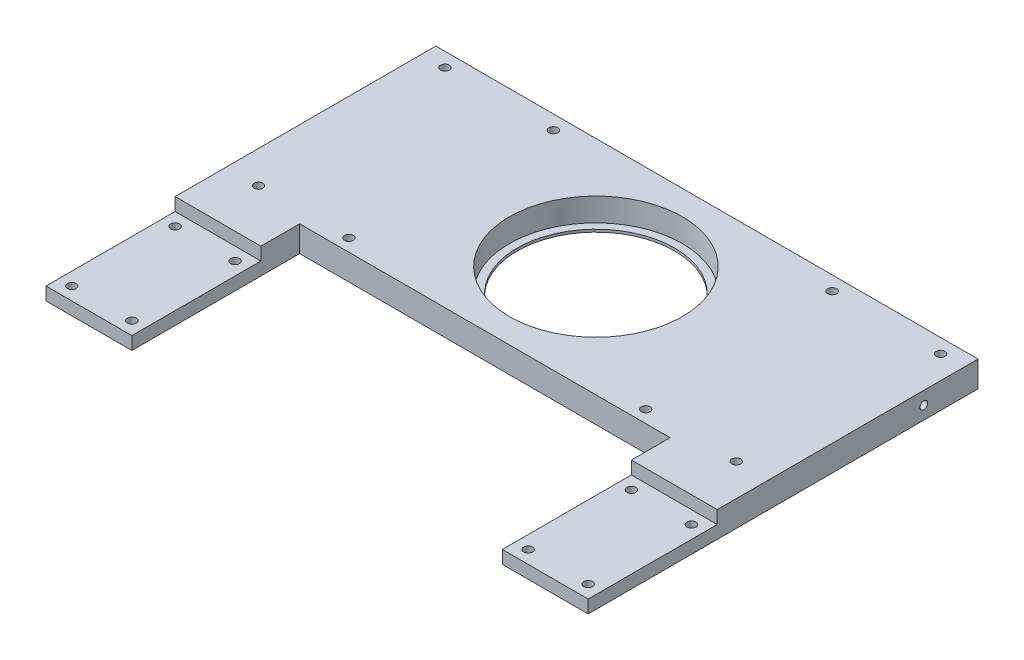
SolidWorks part; units mm, degrees
ref_plane "Ebene vorne" through (0, 0, 0) normal (0, 0, 1) x (1, 0, 0)
ref_plane "Ebene oben" through (0, 0, 0) normal (0, 1, 0) x (1, 0, 0)
ref_plane "Ebene rechts" through (0, 0, 0) normal (1, 0, 0) x (0, 0, -1)
sketch "Skizze1" plane through (0, 0, 0) normal (0, 1, 0) x (1, 0, 0)
  line L1 (-105, -200) -> (105, -200)
  line L2 (-105, -200) -> (-105, 200)
  line L3 (-105, 200) -> (105, 200)
  line L4 (105, -200) -> (105, 200)
  line L5 (-105, -200) -> (105, 200) construction
  line L6 (-105, 200) -> (105, -200) construction
  point P0 (0, 0)
  dimension "D1" = 210
  dimension "D2" = 400
extrude "Aufsatz-Linear austragen1" add sketch "Skizze1" along normal blind 10
ref_plane "Ebene1" through (0, -92.6125, 77.7111) normal (0, -0.766, 0.6428) x (1, 0, 0)
sketch "Skizze2" plane through (0, -92.6125, 77.7111) normal (0, -0.766, 0.6428) x (1, 0, 0)
  line L1 (-105, 159.6368) -> (105, 159.6368) construction
  circle A0 centre (0, 139.6368) radius 5
  dimension "D1" = 10
  dimension "D2" = 20
extrude "Schnitt-Linear austragen1" [suppressed] cut sketch "Skizze2" against normal blind 30 and the other way blind 10
sketch "Skizze3" [suppressed] plane through (0, -67.9923, 57.0523) normal (0, -0.766, 0.6428) x (1, 0, 0)
  circle A0 centre (0, 101.3345) radius 5
  dimension "D1" = 10
extrude "Aufsatz-Linear austragen2" [suppressed] add sketch "Skizze3" along normal blind 0.1
sketch "Skizze4" plane through (0, -92.6125, 77.7111) normal (0, -0.766, 0.6428) x (1, 0, 0)
  line L0 (0, 159.6368) -> (0, 159.9002) construction
  line L1 (-105, 159.6368) -> (105, 159.6368) construction
  line L2 (-25, 159.6368) -> (-25, 194.6368)
  line L3 (-25, 194.6368) -> (25, 194.6368)
  line L4 (-25, 159.6368) -> (25, 159.6368)
  line L5 (25, 159.6368) -> (25, 194.6368)
  point P10 (0, 194.6368)
  dimension "D1" = 50
  dimension "D2" = 35
extrude "Aufsatz-Linear austragen3" [suppressed] add sketch "Skizze4" against normal blind 10 separate body
sketch "Skizze5" plane through (0, 10, 0) normal (0, 1, 0) x (1, 0, 0)
  line L0 (0, 0) -> (0, -200) construction
  line L1 (-105, -200) -> (105, -200) construction
  line L2 (105, -200) -> (18, -200)
  line L3 (-18, -200) -> (-105, -46)
  line L4 (-105, 200) -> (-105, -200) construction
  line L5 (-105, -46) -> (-105, -200)
  line L6 (-105, -200) -> (-18, -200)
  line L7 (105, -46) -> (105, -200)
  line L8 (18, -200) -> (105, -46)
  line L9 (-105, 200) -> (-105, 105)
  line L10 (-105, 105) -> (105, 105)
  line L11 (105, -200) -> (105, 200) construction
  line L12 (105, 105) -> (105, 200)
  line L13 (105, 200) -> (-105, 200)
  line L14 (71.7468, -46) -> (-71.7468, -46)
  line L15 (-71.7468, -46) -> (-2.8247, -168)
  line L16 (71.7468, -46) -> (2.8247, -168)
  line L17 (-2.8247, -168) -> (2.8247, -168)
  line L18 (2.8247, -168) -> (0, -173) construction
  line L19 (-2.8247, -168) -> (0, -173) construction
  point P27 (0, -46)
  dimension "D1" = 36
  dimension "D2" = 154
  dimension "D3" = 95
  dimension "D4" = 32
  dimension "D5" = 27
extrude "Schnitt-Linear austragen2" cut sketch "Skizze5" against normal blind 10
sketch "Skizze6" plane through (0, 10, 0) normal (0, 1, 0) x (1, 0, 0)
  line L0 (0, -200) -> (0, -168) construction
  line L1 (-18, -200) -> (18, -200) construction
  line L2 (-2.8247, -168) -> (2.8247, -168) construction
  line L3 (0, -186.59) -> (-21.075, -186.59) construction
  circle A0 centre (-11, -195) radius 1.7
  circle A1 centre (-11, -178.18) radius 1.7
  circle A2 centre (11, -195) radius 1.7
  circle A3 centre (11, -178.18) radius 1.7
  dimension "D1" = 3.4
  dimension "D2" = 11
  dimension "D3" = 5
  dimension "D4" = 13.41
extrude "Schnitt-Linear austragen3" cut sketch "Skizze6" against normal through all
sketch "Skizze7" plane through (0, 0, 0) normal (0, -1, 0) x (1, 0, 0)
  line L0 (-11, 195) -> (-11, 200) construction
  line L1 (-18, 200) -> (18, 200) construction
  line L2 (-11, 195) -> (-5.1092, 195) construction
  line L3 (-11, 198.4064) -> (-8.05, 196.7032)
  line L4 (-8.05, 196.7032) -> (-8.05, 193.2968)
  line L5 (-11, 191.5936) -> (-8.05, 193.2968)
  line L6 (-11, 191.5936) -> (-13.95, 193.2968)
  line L7 (-13.95, 196.7032) -> (-13.95, 193.2968)
  line L8 (-11, 198.4064) -> (-13.95, 196.7032)
  line L9 (0, 200) -> (0, 121.6034) construction
  line L10 (11, 195) -> (11, 178.18) construction
  line L11 (11, 186.59) -> (0, 186.59) construction
  line L12 (11, 198.4064) -> (8.05, 196.7032)
  line L13 (11, 191.5936) -> (8.05, 193.2968)
  line L14 (8.05, 196.7032) -> (8.05, 193.2968)
  line L15 (11, 191.5936) -> (13.95, 193.2968)
  line L16 (13.95, 196.7032) -> (13.95, 193.2968)
  line L17 (11, 198.4064) -> (13.95, 196.7032)
  line L18 (-8.05, 176.4768) -> (-8.05, 179.8832)
  line L19 (-11, 181.5864) -> (-13.95, 179.8832)
  line L20 (-11, 181.5864) -> (-8.05, 179.8832)
  line L21 (-13.95, 176.4768) -> (-13.95, 179.8832)
  line L22 (-11, 174.7736) -> (-13.95, 176.4768)
  line L23 (-11, 174.7736) -> (-8.05, 176.4768)
  line L24 (8.05, 176.4768) -> (8.05, 179.8832)
  line L25 (11, 181.5864) -> (8.05, 179.8832)
  line L26 (11, 181.5864) -> (13.95, 179.8832)
  line L27 (13.95, 176.4768) -> (13.95, 179.8832)
  line L28 (11, 174.7736) -> (13.95, 176.4768)
  line L29 (11, 174.7736) -> (8.05, 176.4768)
  point P10 (-8.05, 195)
  dimension "D1" = 120
  dimension "D2" = 5.9
extrude "Schnitt-Linear austragen4" cut sketch "Skizze7" against normal blind 4
sketch "Skizze8" plane through (0, 10, 0) normal (0, 1, 0) x (1, 0, 0)
  line L0 (105, 95.41) -> (78.872, 95.41) construction
  line L1 (105, -46) -> (105, 105) construction
  line L2 (-105, 105) -> (105, 105) construction
  dimension "D1" = 9.59
ref_plane "Ebene2" through (0, 52.8485, -44.3452) normal (0, 0.766, -0.6428) x (-1, 0, 0)
sketch "Skizze9" plane through (0, 52.8485, -44.3452) normal (0, 0.766, -0.6428) x (-1, 0, 0)
  line L0 (-105, -66.6604) -> (-78.872, -66.6604) construction
  line L1 (-105, 41.6659) -> (-105, -74.0068) construction
  line L2 (0, -45.2589) -> (0, -16.2619) construction
  circle A0 centre (-100, -66.6604) radius 1.7
  circle A1 centre (100, -66.6604) radius 1.7
  circle A2 centre (-30, -66.6604) radius 1.7
  circle A3 centre (30, -66.6604) radius 1.7
  dimension "D1" = 3.4
  dimension "D2" = 5
  dimension "D3" = 30
extrude "Schnitt-Linear austragen5" [suppressed] cut sketch "Skizze9" against normal through all and the other way through all
ref_plane "Ebene3" through (0, 45.1881, -37.9173) normal (0, 0.766, -0.6428) x (-1, 0, 0)
sketch "Skizze10" [suppressed] plane through (0, 55.0361, -46.1808) normal (0, 0.766, -0.6428) x (-1, 0, 0)
  line L0 (-95, -81.9813) -> (-100, -81.9813) construction
  line L1 (-95, -81.9813) -> (-95, -30.0694) construction
  line L2 (-95, -78.7482) -> (-97.8, -80.3647)
  line L3 (-97.8, -80.3647) -> (-97.8, -83.5979)
  line L4 (-95, -85.2145) -> (-97.8, -83.5979)
  line L5 (-95, -85.2145) -> (-92.2, -83.5979)
  line L6 (-92.2, -80.3647) -> (-92.2, -83.5979)
  line L7 (-95, -78.7482) -> (-92.2, -80.3647)
  line L8 (0, 0) -> (0, -45.6283) construction
  line L9 (-30, -81.9813) -> (-95, -81.9813) construction
  line L10 (-62.5, -81.9813) -> (-62.5, -23.1343) construction
  line L11 (-32.8, -80.3647) -> (-32.8, -83.5979)
  line L12 (-30, -85.2145) -> (-32.8, -83.5979)
  line L13 (-30, -85.2145) -> (-27.2, -83.5979)
  line L14 (-27.2, -80.3647) -> (-27.2, -83.5979)
  line L15 (-30, -78.7482) -> (-27.2, -80.3647)
  line L16 (-30, -78.7482) -> (-32.8, -80.3647)
  line L17 (95, -78.7482) -> (92.2, -80.3647)
  line L18 (92.2, -80.3647) -> (92.2, -83.5979)
  line L19 (95, -85.2145) -> (92.2, -83.5979)
  line L20 (95, -85.2145) -> (97.8, -83.5979)
  line L21 (97.8, -80.3647) -> (97.8, -83.5979)
  line L22 (95, -78.7482) -> (97.8, -80.3647)
  line L23 (30, -78.7482) -> (32.8, -80.3647)
  line L24 (30, -78.7482) -> (27.2, -80.3647)
  line L25 (27.2, -80.3647) -> (27.2, -83.5979)
  line L26 (30, -85.2145) -> (27.2, -83.5979)
  line L27 (30, -85.2145) -> (32.8, -83.5979)
  line L28 (32.8, -80.3647) -> (32.8, -83.5979)
  point P9 (-97.8, -81.9813)
  point P31 (97.8, -81.9813)
  dimension "D1" = 120
  dimension "D2" = 5.6
extrude "Schnitt-Linear austragen6" [suppressed] cut sketch "Skizze10" against normal blind 10 and the other way blind 5
sketch "Skizze13" plane through (0, 10, 0) normal (0, 1, 0) x (1, 0, 0)
  line L0 (71.7468, -46) -> (105, -46) construction
  line L1 (71.7468, -46) -> (96.9548, -60.2409) construction
  line L2 (105, -46) -> (18, -200) construction
  line L3 (0, 0) -> (0, -38.1435) construction
  line L4 (2.8247, -168) -> (71.7468, -46) construction
  line L5 (84.3508, -53.1205) -> (104.4794, -17.4905) construction
  line L6 (105, -46) -> (105, 105) construction
  line L7 (88.3734, -46) -> (88.3734, -1) construction
  line L8 (99, -48.9512) -> (101.4769, -44.5668) construction
  line L9 (87.7845, -76.4734) -> (62.5765, -62.2325) construction
  line L10 (77.1638, -70.4734) -> (91.1741, -70.4734) construction
  circle A0 centre (99, -48.9512) radius 1.7
  circle A1 centre (76.9708, -48.9512) radius 1.7
  circle A2 centre (86.8414, -70.4734) radius 1.7
  circle A3 centre (-86.8414, -70.4734) radius 1.7
  circle A4 centre (-99, -48.9512) radius 1.7
  circle A5 centre (-76.9708, -48.9512) radius 1.7
  dimension "D1" = 6
  dimension "D5" = 35
  dimension "D3" = 3.4
  dimension "D6" = 3.4
  dimension "D2" = 6
  dimension "D4" = 6
extrude "Schnitt-Linear austragen7" [suppressed] cut sketch "Skizze13" against normal through all
sketch "Skizze14" plane through (99.2964, 0, 56.096) normal (0.8707, 0, 0.4919) x (0.4919, 0, -0.8707)
  line L0 (-23.4043, 5) -> (-23.4043, 10)
  line L5 (11.5957, 0) -> (11.5957, 10) construction
  line L6 (-23.4043, 5) -> (11.5957, 5)
  line L7 (11.5957, 10) -> (-165.2799, 10) construction
  line L8 (-23.4043, 10) -> (11.5957, 10)
  line L9 (11.5957, 10) -> (11.5957, 5)
  dimension "D1" = 35
extrude "Schnitt-Linear austragen8" [suppressed] cut sketch "Skizze14" against normal up to surface (28.9525 mm away)
mirror "Spiegeln1" [suppressed] about plane through (0, 0, 0) normal (1, 0, 0)
sketch "Skizze15" [suppressed] plane through (95, 0, 0) normal (1, 0, 0) x (0, 0, -1)
  line L0 (4, 10) -> (4, 0)
  line L1 (4, 0) -> (65, 0)
  line L2 (65, 0) -> (65, 10)
  line L3 (65, 10) -> (4, 10)
extrude "Schnitt-Linear austragen9" [suppressed] cut sketch "Skizze15" against normal through all
sketch "Skizze16" plane through (0, 0, 0) normal (0, -1, 0) x (1, 0, 0)
  line L0 (0, 200) -> (0, 168) construction
  line L1 (-18, 200) -> (18, 200) construction
  line L2 (-2.8247, 168) -> (2.8247, 168) construction
  line L3 (11, 186.59) -> (0, 186.59) construction
  line L4 (11, 195) -> (11, 178.18) construction
  line L6 (-17.5, 183.09) -> (17.5, 183.09)
  line L7 (-17.5, 183.09) -> (-17.5, 190.09)
  line L8 (-17.5, 190.09) -> (17.5, 190.09)
  line L9 (17.5, 183.09) -> (17.5, 190.09)
  line L10 (-17.5, 183.09) -> (17.5, 190.09) construction
  line L11 (-17.5, 190.09) -> (17.5, 183.09) construction
  dimension "D1" = 7
  dimension "D2" = 35
extrude "Schnitt-Linear austragen10" cut sketch "Skizze16" against normal blind 5
sketch "Skizze17" plane through (17.5, 0, 0) normal (-1, 0, 0) x (0, 0, 1)
  line L0 (186.59, 0) -> (186.59, 11.1261) construction
  line L1 (183.09, 0) -> (190.09, 0) construction
  line L2 (183.09, 5) -> (186.59, 8.5)
  line L3 (186.59, 8.5) -> (190.09, 5)
  line L4 (190.09, 5) -> (183.09, 5)
  dimension "D1" = 90
extrude "Schnitt-Linear austragen11" cut sketch "Skizze17" along normal up to surface (35 mm away) up to face at (-17.5, 2.5, 186.59)
sketch "Skizze18" [suppressed] plane through (0, 10, 0) normal (0, 1, 0) x (1, 0, 0)
  line L0 (0, -210) -> (0, 0) construction
  line L1 (-18, -210) -> (18, -210) construction
  line L2 (62.5765, -72.2325) -> (35.4483, -67.5372)
  line L3 (15.3378, -155.8503) -> (-22.1774, -134.6566)
  line L4 (2.8247, -178) -> (62.5765, -72.2325) construction
  line L5 (-15.3378, -155.8503) -> (22.1774, -134.6566)
  line L6 (58.6594, -79.166) -> (40.7308, -76.063)
  line L7 (0, -147.1854) -> (19.5429, -147.1854) construction
  line L8 (0, -95.4) -> (31.4297, -95.4) construction
  line L9 (11.6488, -162.3803) -> (0, -155.7995)
  line L10 (-71.7468, -56) -> (-2.8247, -178) construction
  line L11 (0, -95.4) -> (-37.5153, -116.5937) construction
  line L12 (-37.5153, -116.5937) -> (-39.2566, -117.5774) construction
  line L13 (-11.6488, -162.3803) -> (0, -155.7995)
  line L14 (-58.6594, -79.166) -> (-40.7308, -76.063)
  line L15 (-62.5765, -72.2325) -> (-35.4483, -67.5372)
  circle A0 centre (0, -95.4) radius 33.5
  arc A1 (7.4594, -151.3994) -> (7.4594, -142.9713) centre (9.84, -147.1854) cw
  arc A2 (-7.4594, -151.3994) -> (-7.4594, -142.9713) centre (-9.84, -147.1854) ccw
  circle A3 centre (0, -95.4) radius 45.0879
  point P17 (0, -147.1854)
  point P36 (5, -147.1854)
  point P40 (-5, -147.1854)
  line M16 (62.5765, -72.2325) -> (2.8247, -178)
  line M18 (-2.8247, -178) -> (-71.7468, -56)
  dimension "D2" = 67
  dimension "D5" = 2
  dimension "D4" = 10
  dimension "D1" = 114.6
  dimension "D3" = 7.5
  dimension "D6" = 7.5
extrude "Aufsatz-Linear austragen4" [suppressed] add sketch "Skizze18" against normal blind 10 contours A3 L15 L14 M18 | A3 A0 M16 M18 | A3 L6 L2 M16 | A2 L5 L3 | A3 L3 L5 | L3 A1 L5 | L13 L9 L3 L5 M18 M16
sketch "Skizze19" [suppressed] plane through (0, 0, 0) normal (0, -1, 0) x (1, 0, 0)
  circle A0 centre (0, 35.4) radius 31.5
  circle A1 centre (0, 35.4) radius 33.5
  circle A2 centre (0, 35.4) radius 33.5 construction
  dimension "D1" = 63
extrude "Aufsatz-Linear austragen5" [suppressed] add sketch "Skizze19" against normal blind 1
sketch "Skizze20" plane through (0, 10, 0) normal (0, 1, 0) x (1, 0, 0)
  line L0 (105, 99.52) -> (55.4083, 99.52) construction
  line L1 (105, -46) -> (105, 105) construction
  line L2 (-105, 105) -> (105, 105) construction
  line L3 (0, 105) -> (0, 96.9732) construction
  line L4 (105, 23.82) -> (35.5869, 23.82) construction
  circle A0 centre (96, 99.52) radius 1.7
  circle A1 centre (54, 99.52) radius 1.7
  circle A2 centre (-54, 99.52) radius 1.7
  circle A3 centre (-96, 99.52) radius 1.7
  circle A4 centre (92.5, 23.82) radius 1.7
  circle A5 centre (57.5, 23.82) radius 1.7
  circle A6 centre (-92.5, 23.82) radius 1.7
  circle A7 centre (-57.5, 23.82) radius 1.7
  dimension "D1" = 3.4
  dimension "D2" = 5.48
  dimension "D3" = 9
  dimension "D4" = 42
  dimension "D5" = 75.7
  dimension "D6" = 12.5
  dimension "D7" = 35
extrude "Schnitt-Linear austragen12" cut sketch "Skizze20" against normal through all
sketch "Skizze21" plane through (0, 10, 0) normal (0, 1, 0) x (1, 0, 0)
  line L0 (-71.7468, -46) -> (-71.7468, 19)
  line L1 (-71.7468, 19) -> (71.7468, 19)
  line L2 (71.7468, 19) -> (71.7468, -46)
  line L3 (71.7468, -46) -> (-71.7468, -46) construction
  line L4 (-71.7468, -46) -> (71.7468, -46)
  dimension "D1" = 65
extrude "Schnitt-Linear austragen13" cut sketch "Skizze21" against normal through all
sketch "Skizze22" plane through (0, 10, 0) normal (0, 1, 0) x (1, 0, 0)
  line L0 (-71.7468, -46) -> (-2.8247, -168)
  arc A0 (-71.7468, -46) -> (-2.8247, -168) centre (55.7113, -54.4627) ccw
  line M19 (-2.8247, -168) -> (-71.7468, -46)
extrude "Schnitt-Linear austragen14" cut sketch "Skizze22" against normal through all contours M19 region at (-44.6278, 10, 111.1478)
sketch "Skizze23" plane through (0, 10, 0) normal (0, 1, 0) x (1, 0, 0)
  line L0 (-18, -200) -> (-105, -46) construction
  line L1 (-105, -46) -> (-18, -200)
  arc A0 (-18, -200) -> (-105, -46) centre (108.9155, -26.7263) cw
  arc A2 (-71.7468, -46) -> (-2.8247, -168) centre (55.7113, -54.4627) ccw construction
  dimension "D1" = 60
extrude "Aufsatz-Linear austragen6" add sketch "Skizze23" against normal blind 10
mirror "Spiegeln2" about plane through (0, 0, 0) normal (1, 0, 0) of "Aufsatz-Linear austragen6", "Schnitt-Linear austragen14"
sketch "Skizze25" plane through (0, 10, 0) normal (0, 1, 0) x (1, 0, 0)
  line L0 (-105, -46) -> (-71.7468, -46) construction
  line L1 (-105, 4) -> (-105, -46) construction
  line L2 (-105, 4) -> (-71.7468, 4) construction
  line L3 (-71.7468, 19) -> (-71.7468, -46) construction
  line L4 (-88.3734, 4) -> (-88.3734, -46) construction
  line L5 (-105, -21) -> (-71.7468, -21) construction
  line L6 (-105, 105) -> (-105, -46) construction
  circle A0 centre (-100, -1) radius 1.7
  circle A1 centre (-76.7468, -1) radius 1.7
  circle A2 centre (-76.7468, -41) radius 1.7
  circle A3 centre (-100, -41) radius 1.7
  dimension "D2" = 3.4
  dimension "D1" = 50
  dimension "D3" = 5
  dimension "D4" = 5
extrude "Schnitt-Linear austragen15" cut sketch "Skizze25" against normal through all
sketch "Skizze26" plane through (-105, 0, 0) normal (-1, 0, 0) x (0, 0, 1)
  line L0 (-4, 5) -> (-4, 13.1015)
  line L1 (46, 0) -> (46, 10) construction
  line L2 (46, 5) -> (-4, 5)
  line L4 (-105, 0) -> (46, 0) construction
  line L5 (46, 5) -> (46, 0)
  line L6 (-4, 13.1015) -> (200.6846, 82.5463)
  line L7 (200.6846, 82.5463) -> (242.9972, -41.0376)
  line L8 (242.9972, -41.0376) -> (91.2415, -60.2848)
  line L9 (91.2415, -60.2848) -> (46, 0)
  dimension "D1" = 50
mirror "Spiegeln3" about plane through (0, 0, 0) normal (1, 0, 0) of "Schnitt-Linear austragen15"
extrude "Schnitt-Linear austragen16" cut sketch "Skizze26" against normal through all
sketch "Skizze27" plane through (0, 10, 0) normal (0, 1, 0) x (1, 0, 0)
  line L0 (0, 19) -> (0, 105) construction
  line L1 (71.7468, 19) -> (-71.7468, 19) construction
  line L2 (-105, 105) -> (105, 105) construction
  circle A0 centre (0, 62) radius 33.5
  dimension "D1" = 67
extrude "Schnitt-Linear austragen17" cut sketch "Skizze27" against normal through all
sketch "Skizze28" plane through (0, 0, 0) normal (0, -1, 0) x (1, 0, 0)
  circle A0 centre (0, -62) radius 30.5
  circle A1 centre (0, -62) radius 33.5 construction
  circle A2 centre (0, -62) radius 36.0063
  dimension "D1" = 3
extrude "Aufsatz-Linear austragen7" add sketch "Skizze28" against normal blind 1
sketch "Skizze29" plane through (-105, 0, 0) normal (-1, 0, 0) x (0, 0, 1)
  line L0 (-105, 5) -> (-93.4233, 5) construction
  line L1 (-105, 0) -> (-105, 10) construction
  circle A0 centre (-84, 5) radius 1.5
  dimension "D1" = 3
  dimension "D2" = 21
extrude "Schnitt-Linear austragen18" cut sketch "Skizze29" against normal blind 10
sketch "Skizze30" plane through (0, 0, -105) normal (0, 0, -1) x (-1, 0, 0)
  line L0 (105, 5) -> (60.2539, 5) construction
  line L1 (105, 0) -> (105, 10) construction
  circle A0 centre (100, 5) radius 1.5
  circle A1 centre (84, 5) radius 1.5
  dimension "D1" = 3
  dimension "D2" = 5
  dimension "D3" = 21
extrude "Schnitt-Linear austragen19" cut sketch "Skizze30" against normal blind 10
mirror "Spiegeln4" about plane through (0, 0, 0) normal (1, 0, 0) of "Schnitt-Linear austragen18", "Schnitt-Linear austragen19"
sketch "Skizze31" plane through (0, 0, 0) normal (0, -1, 0) x (1, 0, 0)
  line L0 (0, -105) -> (0, -73.0202) construction
  line L1 (-105, -105) -> (105, -105) construction
  circle A0 centre (-96, -99.52) radius 2.95
  circle A1 centre (-54, -99.52) radius 2.95
  circle A2 centre (-92.5, -23.82) radius 2.95
  circle A3 centre (-57.5, -23.82) radius 2.95
  circle A4 centre (57.5, -23.82) radius 2.95
  circle A5 centre (92.5, -23.82) radius 2.95
  circle A6 centre (54, -99.52) radius 2.95
  circle A7 centre (96, -99.52) radius 2.95
  dimension "D1" = 5.9
extrude "Schnitt-Linear austragen20" cut sketch "Skizze31" against normal blind 3.5
